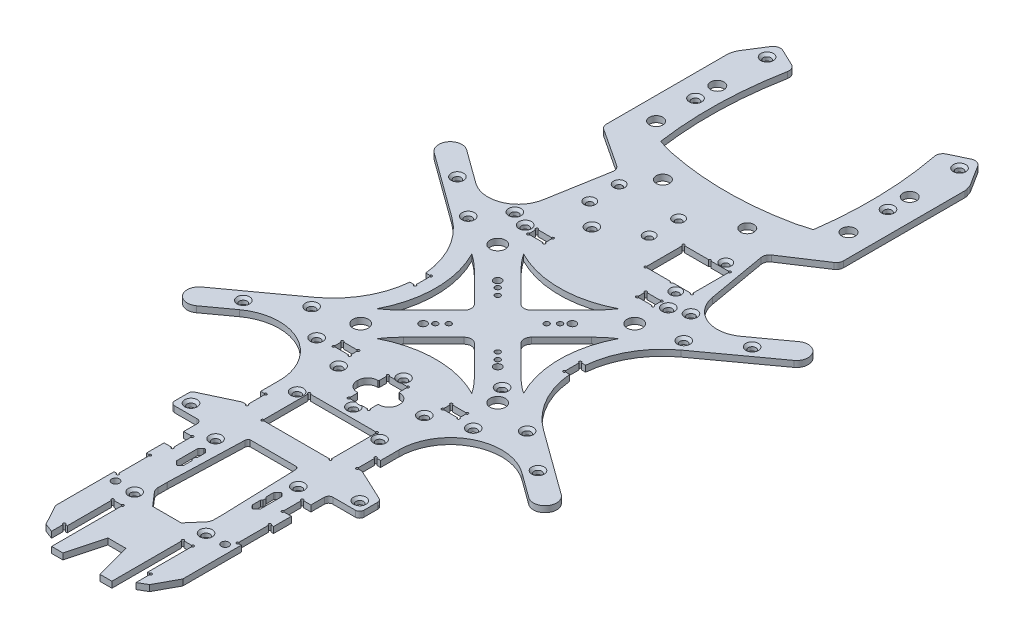
SolidWorks part; units mm, degrees
material "PPS"
ref_plane "前视基准面" through (0, 0, 0) normal (0, 0, 1) x (1, 0, 0)
ref_plane "上视基准面" through (0, 0, 0) normal (0, 1, 0) x (1, 0, 0)
ref_plane "右视基准面" through (0, 0, 0) normal (1, 0, 0) x (0, 0, -1)
sketch "草图1" plane through (0, 0, 0) normal (0, 1, 0) x (1, 0, 0)
  line L0 (-126.4995, 0) -> (116.8967, 0) construction
  line L1 (121.619, 121.619) -> (-121.619, -121.619) construction
  line L2 (0, 104.5414) -> (0, -99.6328) construction
  line L3 (-108.3893, 108.3893) -> (124.9236, -124.9236) construction
  line L4 (0, 0) -> (86.3378, -62.728) construction
  line L5 (21.4, 65.75) -> (28.6, 65.75)
  line L6 (20.9, 50.75) -> (20.9, 65.25)
  line L19 (21.4, 50.25) -> (28.6, 50.25)
  line L20 (30.0249, 79.2189) -> (48.4165, 91.3178)
  line L21 (0, 82.79) -> (0, 88.225) construction
  line L23 (-25.2781, 96.1111) -> (-31.2329, 97.7907)
  line L25 (24.5, -95.1) -> (26, -95.1) construction
  line L35 (73.5338, -47.5541) -> (46.853, -28.1694)
  line L38 (-14.1474, -105.2622) -> (-15.2326, -104.177)
  line L39 (-48.4165, 91.3178) -> (-48.4165, 143.0516)
  line L40 (-30.0249, 79.2189) -> (-48.4165, 91.3178)
  line L42 (26, -95.1) -> (26, -102.35)
  line L64 (20.9, 58) -> (32.4846, 58) construction
  line L65 (25, 65.75) -> (25, 50.25) construction
  line L66 (29.1, 65.25) -> (29.1, 50.75)
  line L69 (-39.335, 68.135) -> (3.7462, 68.135) construction
  line L72 (26, -102.35) -> (22.5, -102.35)
  line L80 (-15.9397, -104.177) -> (-16.9545, -105.1918)
  line L82 (4.1009, -56.25) -> (4.1009, -53.2975)
  line L83 (-3.6009, -56.75) -> (3.6009, -56.75)
  line L84 (3.6009, -40.75) -> (-3.5991, -40.75)
  line L85 (4.1009, -41.25) -> (4.1009, -44.2025)
  line L86 (-4.1009, -56.25) -> (-4.1009, -53.2961)
  line L87 (-4.1009, -44.2011) -> (-4.1009, -41.2481)
  line L88 (-4.5484, -52.9461) -> (-4.4509, -52.9461)
  line L89 (-8.5484, -48.9461) -> (-8.5484, -48.5511)
  line L90 (8.5484, -48.9475) -> (8.5484, -48.5525)
  line L91 (4.4509, -52.9475) -> (4.5484, -52.9475)
  line L92 (4.5484, -44.5525) -> (4.4509, -44.5525)
  line L93 (-4.5484, -44.5511) -> (-4.4509, -44.5511)
  line L97 (19, -62.5) -> (19, -100.5) construction
  line L98 (19, -100.5) -> (-19, -100.5) construction
  line L99 (-19, -62.5) -> (-19, -100.5) construction
  line L100 (22.5, -102.35) -> (22.5, -110.35)
  line L101 (16.4174, -141.0041) -> (16.4174, -159.5041)
  line L102 (16.4174, -141.0041) -> (12.3174, -141.0041)
  line L103 (12.3174, -141.0041) -> (12.3174, -170.0041)
  line L104 (17.705, -159.5041) -> (16.4174, -159.5041)
  line L105 (17.705, -165.5542) -> (17.705, -159.5041)
  line L106 (-3.8169, -155.5041) -> (-7.6919, -170.0041)
  line L107 (-7.6919, -170.0041) -> (-12.3174, -170.0041)
  line L108 (21.2406, -163.4622) -> (17.705, -165.5542)
  line L109 (-17.705, -164.6632) -> (-17.705, -159.5041)
  line L110 (-17.705, -159.5041) -> (-16.4174, -159.5041)
  line L111 (-12.3174, -141.0041) -> (-12.3174, -170.0041)
  line L112 (-16.4174, -141.0041) -> (-12.3174, -141.0041)
  line L113 (-16.4174, -141.0041) -> (-16.4174, -159.5041)
  line L114 (7.4592, -170.0041) -> (12.3174, -170.0041)
  line L115 (-3.8169, -155.5041) -> (3.6009, -155.5041)
  line L116 (3.6009, -155.5041) -> (7.4592, -170.0041)
  line L117 (-21.3412, -163.277) -> (-17.705, -164.6632)
  line L118 (-11.3955, -123.6362) -> (-10.3849, -92.9161)
  line L119 (-10.5767, -129.7197) -> (-5.85, -135.1929)
  line L120 (-5.85, -135.1929) -> (5.85, -135.1929)
  line L121 (-11.3974, -127.5138) -> (-11.3974, -123.7472)
  line L122 (22.5, -110.35) -> (26, -110.35)
  line L123 (26, -130.7962) -> (26, -154.7028)
  line L124 (26, -154.7028) -> (21.2406, -163.4622)
  line L125 (-26, -154.7028) -> (-21.3412, -163.277)
  line L126 (-26, -130.7962) -> (-26, -154.7028)
  line L127 (26, -110.35) -> (26, -117.6)
  line L128 (26, -117.6) -> (24.5, -117.6)
  line L129 (24.5, -117.6) -> (24.5, -130.7962)
  line L130 (24.5, -130.7962) -> (26, -130.7962)
  line L132 (-24.5, -130.7962) -> (-26, -130.7962)
  line L133 (-24.5, -117.6) -> (-24.5, -130.7962)
  line L134 (-26, -117.6) -> (-24.5, -117.6)
  line L135 (-26, -110.35) -> (-26, -117.6)
  line L136 (-22.5, -110.35) -> (-26, -110.35)
  line L137 (-22.5, -102.35) -> (-22.5, -110.35)
  line L138 (-26, -102.35) -> (-22.5, -102.35)
  line L139 (-26, -95.1) -> (-26, -102.35)
  line L140 (-24.5, -95.1) -> (-26, -95.1) construction
  line L142 (-73.5338, 47.5541) -> (-46.853, 28.1694)
  line L143 (-73.5338, -47.5541) -> (-46.853, -28.1694)
  line L149 (48.4165, 91.3178) -> (48.4165, 143.0516)
  line L150 (0, -114.8485) -> (0, -146.3095) construction
  line L151 (-9.5, -91.6929) -> (9.5, -91.6929)
  line L152 (10.5767, -129.7197) -> (5.85, -135.1929)
  line L153 (11.3974, -127.5138) -> (11.3974, -123.7472)
  line L154 (11.3955, -123.6362) -> (10.3849, -92.9161)
  line L155 (-19, -62.5) -> (19, -62.5) construction
  line L166 (-13.866, -63.21) -> (13.866, -63.21)
  line L171 (-13.866, -63.21) -> (-13.866, -82.21)
  line L174 (-13.866, -82.21) -> (13.866, -82.21)
  line L177 (13.866, -63.21) -> (13.866, -82.21)
  line L180 (73.5338, 47.5541) -> (46.853, 28.1694)
  line L181 (44.0442, 32) -> (60.2246, 43.7557) construction
  line L183 (25.2781, 96.1111) -> (31.2329, 97.7907)
  line L184 (47.6512, 145.4189) -> (48.4165, 143.0516)
  line L188 (-47.6512, 145.4189) -> (-40.8875, 156.1591)
  line L190 (47.6512, 145.4189) -> (40.8875, 156.1591)
  line L192 (31.6811, 151.7709) -> (40.8875, 156.1591)
  line L193 (-40.8875, 156.1591) -> (-31.6811, 151.7709)
  line L194 (-47.6512, 145.4189) -> (-48.4165, 143.0516)
  line L195 (67.9498, 55.2397) -> (54.1532, 45.2159)
  line L196 (30.0249, 79.2189) -> (34.5797, 53.1425)
  line L197 (-30.0249, 79.2189) -> (-34.5797, 53.1425)
  line L198 (-67.9498, 55.2397) -> (-54.1532, 45.2159)
  line L199 (57.77, -47.8437) -> (67.9498, -55.2397)
  line L200 (24.5, -64.7956) -> (24.5, -95.1) construction
  line L201 (-24.5, -64.7956) -> (-24.5, -95.1) construction
  line L202 (-57.77, -47.8437) -> (-67.9498, -55.2397)
  line L203 (26, -95.1) -> (38.6804, -95.1)
  line L204 (38.6804, -95.1) -> (38.6804, -86.6)
  line L205 (38.6804, -86.6) -> (24.5, -79.9478)
  line L207 (-38.6804, -86.6) -> (-24.5, -79.9478)
  line L208 (-38.6804, -95.1) -> (-38.6804, -86.6)
  line L209 (-26, -95.1) -> (-38.6804, -95.1)
  line L210 (-24.5, -64.7956) -> (-24.5, -79.9478) construction
  line L211 (-16.9545, -114.3989) -> (-15.8693, -115.4841)
  line L212 (-15.1622, -115.4841) -> (-14.1474, -114.4693)
  line L213 (-17.1009, -105.5454) -> (-17.1009, -114.0454)
  line L214 (-14.0009, -105.6158) -> (-14.0009, -114.1158) construction
  line L221 (-14.0009, -105.6158) -> (-14.0009, -108.6704)
  line L222 (-14.0009, -108.6704) -> (-14.5009, -109.1704)
  line L223 (-14.5009, -109.1704) -> (-14.5009, -110.4204)
  line L224 (-14.5009, -110.4204) -> (-14.0009, -110.9204)
  line L225 (-14.0009, -110.9204) -> (-14.0009, -114.1158)
  line L226 (-17.1009, -109.7954) -> (-13.2317, -109.7954) construction
  line L227 (14.5009, -110.4204) -> (14.0009, -110.9204)
  line L228 (14.5009, -109.1704) -> (14.5009, -110.4204)
  line L229 (14.0009, -108.6704) -> (14.5009, -109.1704)
  line L230 (14.0009, -105.6158) -> (14.0009, -108.6704)
  line L231 (14.1474, -105.2622) -> (15.2326, -104.177)
  line L232 (15.9397, -104.177) -> (16.9545, -105.1918)
  line L233 (17.1009, -105.5454) -> (17.1009, -114.0454)
  line L234 (16.9545, -114.3989) -> (15.8693, -115.4841)
  line L235 (15.1622, -115.4841) -> (14.1474, -114.4693)
  line L236 (14.0009, -110.9204) -> (14.0009, -114.1158)
  line L237 (-24.5, -72.3717) -> (-22.5, -72.3717)
  line L238 (-22.5, -72.3717) -> (-22.5, -79.9478)
  line L239 (-22.5, -79.9478) -> (-24.5, -79.9478)
  line L240 (-24.5, -64.7956) -> (-24.5, -72.3717)
  line L241 (22.5, -79.9478) -> (24.5, -79.9478)
  line L242 (24.5, -64.7956) -> (24.5, -72.3717)
  line L243 (24.5, -72.3717) -> (22.5, -72.3717)
  line L244 (22.5, -72.3717) -> (22.5, -79.9478)
  circle A0 centre (10, 10) radius 1.075
  circle A1 centre (12.75, 12.75) radius 1.075
  circle A2 centre (15.25, 15.25) radius 1.55
  circle A3 centre (-15.25, 15.25) radius 1.55
  circle A4 centre (-12.75, 12.75) radius 1.075
  circle A5 centre (-10, 10) radius 1.075
  circle A6 centre (-10, -10) radius 1.075
  circle A7 centre (-12.75, -12.75) radius 1.075
  circle A8 centre (-15.25, -15.25) radius 1.55
  circle A9 centre (15.25, -15.25) radius 1.55
  circle A10 centre (12.75, -12.75) radius 1.075
  circle A11 centre (10, -10) radius 1.075
  circle A14 centre (28, -28) radius 3.15
  circle A15 centre (-28, -28) radius 3.15
  circle A16 centre (25, 68.2) radius 1.3
  arc A17 (20.9, 65.25) -> (21.4, 65.75) centre (20.9, 65.75) cw
  arc A18 (20.9, 50.75) -> (21.4, 50.25) centre (20.9, 50.25) ccw
  circle A31 centre (25, 47.8) radius 1.3
  circle A34 centre (17.238, 84.7633) radius 2.75
  circle A35 centre (-17.238, 84.7633) radius 2.75
  circle A36 centre (-39.335, 104.0823) radius 2.75
  circle A37 centre (-39.335, 129.0823) radius 2.75
  circle A38 centre (-28, 28) radius 3.15
  circle A39 centre (28, 28) radius 3.15
  circle A43 centre (44.0442, -32) radius 1.55
  circle A44 centre (60.2246, -43.7557) radius 1.55
  circle A47 centre (-60.2246, -43.7557) radius 1.55
  arc A63 (29.1, 65.25) -> (28.6, 65.75) centre (29.1, 65.75) ccw
  arc A64 (29.1, 50.75) -> (28.6, 50.25) centre (29.1, 50.25) cw
  circle A65 centre (-24.5, 74.15) radius 1.3
  circle A68 centre (-24.5, 62.12) radius 1.3
  circle A71 centre (-44.0442, -32) radius 1.55
  circle A72 centre (60.2246, 43.7557) radius 1.55
  circle A73 centre (44.0442, 32) radius 1.55
  circle A74 centre (-44.0442, 32) radius 1.55
  circle A75 centre (-60.2246, 43.7557) radius 1.55
  arc A77 (67.9498, -55.2397) -> (73.5338, -47.5541) centre (70.7418, -51.3969) ccw
  arc A82 (-14.0009, -105.6158) -> (-14.1474, -105.2622) centre (-14.5009, -105.6158) ccw
  arc A83 (-15.2326, -104.177) -> (-15.9397, -104.177) centre (-15.5861, -104.5306) ccw
  arc A84 (-17.1009, -105.5454) -> (-16.9545, -105.1918) centre (-16.6009, -105.5454) cw
  arc A85 (-4.1009, -56.25) -> (-3.6009, -56.75) centre (-4.1009, -56.75) ccw
  arc A86 (4.1009, -56.25) -> (3.6009, -56.75) centre (4.1009, -56.75) cw
  arc A87 (4.1009, -41.25) -> (3.6009, -40.75) centre (4.1009, -40.75) ccw
  arc A88 (-4.1009, -41.2481) -> (-3.5991, -40.75) centre (-4.0991, -40.7481) cw
  arc A89 (8.5484, -48.5525) -> (4.5484, -44.5525) centre (4.5484, -48.5525) ccw
  arc A90 (-4.5484, -44.5511) -> (-8.5484, -48.5511) centre (-4.5484, -48.5511) ccw
  arc A91 (-4.5484, -52.9461) -> (-8.5484, -48.9461) centre (-4.5484, -48.9461) cw
  arc A92 (8.5484, -48.9475) -> (4.5484, -52.9475) centre (4.5484, -48.9475) cw
  arc A93 (4.1009, -44.2025) -> (4.4509, -44.5525) centre (4.4509, -44.2025) ccw
  arc A94 (4.1009, -53.2975) -> (4.4509, -52.9475) centre (4.4509, -53.2975) cw
  arc A95 (-4.1009, -44.2011) -> (-4.4509, -44.5511) centre (-4.4509, -44.2011) cw
  arc A96 (-4.1009, -53.2961) -> (-4.4509, -52.9461) centre (-4.4509, -53.2961) ccw
  circle A103 centre (-22.3899, -133.8062) radius 1.55
  circle A104 centre (22.3899, -133.8062) radius 1.55
  circle A105 centre (-16.9, -98.4) radius 1.55
  circle A106 centre (16.9, -98.4) radius 1.55
  arc A107 (-9.5, -91.6929) -> (-10.3849, -92.9161) centre (-9.0356, -92.9605) ccw
  arc A108 (-11.3974, -123.7472) -> (-11.3955, -123.6362) centre (-8.0224, -123.7472) cw
  arc A109 (-10.5767, -129.7197) -> (-11.3974, -127.5138) centre (-8.0224, -127.5138) cw
  circle A110 centre (-14.6009, -133.8062) radius 1.55
  circle A111 centre (14.6009, -133.8062) radius 1.55
  arc A112 (10.5767, -129.7197) -> (11.3974, -127.5138) centre (8.0224, -127.5138) ccw
  arc A113 (11.3974, -123.7472) -> (11.3955, -123.6362) centre (8.0224, -123.7472) ccw
  arc A114 (9.5, -91.6929) -> (10.3849, -92.9161) centre (9.0356, -92.9605) cw
  circle A143 centre (-16.866, -65.108) radius 1.55
  circle A144 centre (16.866, -65.108) radius 1.55
  circle A145 centre (0, -38.5) radius 1.55
  circle A146 centre (0, -59) radius 1.55
  arc A147 (67.9498, 55.2397) -> (73.5338, 47.5541) centre (70.7418, 51.3969) cw
  arc A148 (46.853, 28.1694) -> (46.853, -28.1694) centre (67.3193, 0) ccw
  circle A149 centre (44.0442, -32) radius 6 construction
  arc A151 (-67.9498, 55.2397) -> (-73.5338, 47.5541) centre (-70.7418, 51.3969) ccw
  arc A153 (-46.853, 28.1694) -> (-46.853, -28.1694) centre (-67.3193, 0) cw
  arc A154 (-67.9498, -55.2397) -> (-73.5338, -47.5541) centre (-70.7418, -51.3969) cw
  circle A158 centre (39.335, 129.0823) radius 2.75
  circle A159 centre (39.335, 104.0823) radius 2.75
  arc A160 (-25.2781, 96.1111) -> (25.2781, 96.1111) centre (0, 215.2587) ccw
  circle A161 centre (-36, 43) radius 1.55
  circle A164 centre (36, 43) radius 1.55
  circle A165 centre (-32, -42) radius 1.55
  circle A166 centre (32, -42) radius 1.55
  circle A171 centre (-39.335, 149.4323) radius 1.55
  arc A176 (30.0249, 148.5011) -> (31.6811, 151.7709) centre (32.9719, 149.0628) cw
  arc A178 (30.0249, 148.5011) -> (31.2329, 97.7907) centre (-122.0773, 119.5082) cw
  arc A180 (-30.0249, 148.5011) -> (-31.2329, 97.7907) centre (122.0773, 119.5082) ccw
  arc A181 (-31.6811, 151.7709) -> (-30.0249, 148.5011) centre (-32.9719, 149.0628) cw
  arc A182 (54.1532, 45.2159) -> (34.5797, 53.1425) centre (46.8385, 55.2837) cw
  arc A183 (-54.1532, 45.2159) -> (-34.5797, 53.1425) centre (-46.8385, 55.2837) ccw
  circle A185 centre (39.335, 149.4323) radius 1.55
  arc A186 (57.77, -47.8437) -> (24.5, -64.7956) centre (45.4537, -64.7956) ccw
  arc A187 (-57.77, -47.8437) -> (-24.5, -64.7956) centre (-45.4537, -64.7956) cw
  circle A188 centre (34.5, -90.85) radius 1.55
  circle A189 centre (-34.5, -90.85) radius 1.55
  circle A190 centre (39.335, 120.1823) radius 1.55
  circle A191 centre (-39.335, 120.1823) radius 1.55
  arc A192 (-17.1009, -114.0454) -> (-16.9545, -114.3989) centre (-16.6009, -114.0454) ccw
  arc A193 (-15.8693, -115.4841) -> (-15.1622, -115.4841) centre (-15.5157, -115.1306) ccw
  arc A194 (-14.0009, -114.1158) -> (-14.1474, -114.4693) centre (-14.5009, -114.1158) cw
  arc A195 (14.0009, -105.6158) -> (14.1474, -105.2622) centre (14.5009, -105.6158) cw
  arc A196 (15.2326, -104.177) -> (15.9397, -104.177) centre (15.5861, -104.5306) cw
  arc A197 (17.1009, -105.5454) -> (16.9545, -105.1918) centre (16.6009, -105.5454) ccw
  arc A198 (17.1009, -114.0454) -> (16.9545, -114.3989) centre (16.6009, -114.0454) cw
  arc A199 (15.8693, -115.4841) -> (15.1622, -115.4841) centre (15.5157, -115.1306) cw
  arc A200 (14.0009, -114.1158) -> (14.1474, -114.4693) centre (14.5009, -114.1158) ccw
  circle A201 centre (-0.2, 62.12) radius 1.3
  circle A202 centre (-0.2, 74.15) radius 1.3
  point P104 (-32.5, 0)
  point P105 (32.5, 0)
  point P214 (38.6804, -90.85)
  point P354 (0, -135.1929)
  point P361 (7.3036, -118.1341)
  point P364 (0, -91.6929)
  dimension "D2" = 2.15
  dimension "D5" = 3.1
  dimension "D7" = 3.1
  dimension "D8" = 36
  dimension "D10" = 0.5
  dimension "D11" = 3.1
  dimension "D20" = 2.6
  dimension "D22" = 3.1
  dimension "D32" = 7.25
  dimension "D12" = 24.3
  dimension "D15" = 19
  dimension "D13" = 3
  dimension "D9" = 3.1
  dimension "D25" = 4.75
  dimension "D26" = 13
  dimension "D31" = 12
  dimension "D41" = 96.833
  dimension "D49" = 32
  dimension "D54" = 45.35
  dimension "D59" = 8.5
  dimension "D61" = 6.3
  dimension "D70" = 2.6
  dimension "D3" = 10
  dimension "D4" = 2.75
  dimension "D6" = 2.5
  dimension "D14" = 58
  dimension "D16" = 2.608
  dimension "D17" = 15.5
  dimension "D18" = 2.45
  dimension "D19" = 8.2
  dimension "D21" = 12.03
  dimension "D23" = 2.25
  dimension "D24" = 2.25
  dimension "D27" = 20
  dimension "D28" = 25
  dimension "D29" = 25
  dimension "D30" = 32
  dimension "D33" = 1.5
  dimension "D34" = 2.1
  dimension "D35" = 10.5
  dimension "D36" = 14.5
  dimension "D37" = 4
  dimension "D38" = 4.1
  dimension "D39" = 8
  dimension "D40" = 65
  dimension "D42" = 9.5
  dimension "D43" = 43
  dimension "D44" = 43.5
  dimension "D45" = 40.75
  dimension "D46" = 7.2
  dimension "D47" = 16
  dimension "D48" = 62.5
  dimension "D50" = 38
  dimension "D51" = 7.2
  dimension "D52" = 36
  dimension "D53" = 42
  dimension "D55" = 90.85
  dimension "D56" = 5.5
  dimension "D57" = 38
  dimension "D58" = 34.5
  dimension "D60" = 56
  dimension "D62" = 5.85
  dimension "D63" = 29.25
  dimension "D64" = 8.5
  dimension "D65" = 1.25
  dimension "D66" = 0.5
  dimension "D67" = 2
  dimension "D68" = 24.5
  dimension "D69" = 82.21
extrude "凸台-拉伸1" add sketch "草图1" along normal blind 2.5
sketch "草图6" plane through (0, 2.5, 0) normal (0, 1, 0) x (1, 0, 0)
  line L1 (-23.978, 14.4296) -> (-9.5485, 0)
  line L2 (-126.4995, 0) -> (116.8967, 0) construction
  line L3 (-58.8867, 0) -> (57.6096, 0) construction
  line L4 (-23.978, -14.4296) -> (-9.5485, 0)
  line L5 (0, 29.8455) -> (0, -115.5328) construction
  line L6 (0, 104.5414) -> (0, -99.6328) construction
  line L14 (14.4296, 23.978) -> (0, 9.5485)
  line L15 (-14.4296, 23.978) -> (0, 9.5485)
  line L27 (23.978, -14.4296) -> (9.5485, 0)
  line L28 (23.978, 14.4296) -> (9.5485, 0)
  line L29 (-14.4296, -23.978) -> (0, -9.5485)
  line L30 (14.4296, -23.978) -> (0, -9.5485)
  arc A3 (-23.978, 14.4296) -> (-29.9602, 19.3706) centre (-52.8883, -14.4807) ccw
  arc A5 (-23.978, -14.4296) -> (-29.9602, -19.3706) centre (-52.8883, 14.4807) cw
  arc A6 (-29.9602, -19.3706) -> (-29.9602, 19.3706) centre (-67.3193, 0) ccw
  arc A18 (-14.4296, 23.978) -> (-19.3706, 29.9602) centre (14.4807, 52.8883) cw
  arc A19 (-19.3706, 29.9602) -> (19.3706, 29.9602) centre (0, 67.3193) ccw
  arc A20 (14.4296, 23.978) -> (19.3706, 29.9602) centre (-14.4807, 52.8883) ccw
  arc A30 (23.978, 14.4296) -> (29.9602, 19.3706) centre (52.8883, -14.4807) cw
  arc A31 (29.9602, 19.3706) -> (29.9602, -19.3706) centre (67.3193, 0) ccw
  arc A32 (23.978, -14.4296) -> (29.9602, -19.3706) centre (52.8883, 14.4807) ccw
  arc A33 (14.4296, -23.978) -> (19.3706, -29.9602) centre (-14.4807, -52.8883) cw
  arc A34 (19.3706, -29.9602) -> (-19.3706, -29.9602) centre (0, -67.3193) ccw
  arc A35 (-14.4296, -23.978) -> (-19.3706, -29.9602) centre (14.4807, -52.8883) ccw
  dimension "D1" = 45
  dimension "D2" = 4
extrude "减重" cut sketch "草图6" against normal up to next
fillet "圆角1" radius 3 14 edges at (-25.2781, 1.25, -96.1111) (25.2781, 1.25, -96.1111) (48.4165, 1.25, -91.3178) (-48.4165, 1.25, -91.3178) (-9.5485, 1.25, 0) (9.5485, 1.25, 0) (0, 1.25, -9.5485) (0, 1.25, 9.5485) (48.4165, 1.25, -143.0516) (40.8875, 1.25, -156.1591) (-48.4165, 1.25, -143.0516) (-40.8875, 1.25, -156.1591) (-30.0249, 1.25, -79.2189) (30.0249, 1.25, -79.2189)
sketch "草图7" plane through (0, 2.5, 0) normal (0, 1, 0) x (1, 0, 0)
  line L0 (-81.2345, 0) -> (102.1666, 0) construction
  line L1 (0, 63.5408) -> (0, -83.9036) construction
  line L2 (34, -3.25) -> (30.5, -3.25)
  line L3 (-34, 3.25) -> (-30.5, 3.25)
  line L4 (-34, 3.25) -> (-34, -3.25)
  line L5 (-34, -3.25) -> (-30.5, -3.25)
  line L6 (-30.5, 3.25) -> (-30.5, -3.25)
  line L7 (30.5, 3.25) -> (30.5, -3.25)
  line L8 (34, 3.25) -> (30.5, 3.25)
  line L9 (34, 3.25) -> (34, -3.25)
  line L10 (19, -38) -> (25.5, -38)
  line L11 (-25.5, 41.5) -> (-19, 41.5)
  line L12 (-25.5, 41.5) -> (-25.5, 38)
  line L13 (-25.5, 38) -> (-19, 38)
  line L14 (-19, 41.5) -> (-19, 38)
  line L15 (19, -38) -> (19, -41.5)
  line L16 (19, -41.5) -> (25.5, -41.5)
  line L17 (25.5, -38) -> (25.5, -41.5)
  line L18 (-19, -38) -> (-19, -41.5)
  line L19 (-19, -41.5) -> (-25.5, -41.5)
  line L20 (-25.5, -38) -> (-25.5, -41.5)
  line L21 (-19, -38) -> (-25.5, -38)
  line L22 (25.5, 38) -> (19, 38)
  line L23 (19, 41.5) -> (19, 38)
  line L24 (25.5, 41.5) -> (19, 41.5)
  line L25 (25.5, 41.5) -> (25.5, 38)
  point P26 (19, -39.75)
  dimension "D1" = 3.5
  dimension "D2" = 6.5
  dimension "D3" = 30.5
  dimension "D4" = 38
  dimension "D5" = 19
  dimension "D6" = 38
extrude "保护壳固定点" cut sketch "草图7" against normal up to next
sketch "草图8" plane through (0, 0, 0) normal (0, 1, 0) x (1, 0, 0)
  line L5 (0, 0) -> (0, 133.3353) construction
  line L6 (0, 0) -> (133.1914, 0) construction
  line L7 (10.15, 65.7804) -> (20.9, 65.7804)
  line L8 (20.9, 65.25) -> (20.9, 50.75) construction
  line L9 (20.9, 65.7804) -> (20.9, 50.2804)
  line L10 (20.9, 50.2804) -> (10.15, 50.2804)
  line L11 (10.15, 50.2804) -> (10.15, 65.7804)
  line L12 (19.65, 65.7804) -> (19.65, 50.2804) construction
  circle A0 centre (23.5, -21.7128) radius 1.55
  circle A1 centre (0, -38.5) radius 1.55 construction
  circle A2 centre (-29.25, 40.5) radius 1.55
  circle A4 centre (-17.5, -47.5) radius 1.55
  circle A6 centre (29.25, 40.5) radius 1.55
  circle A7 centre (17.5, -47.5) radius 1.55
  circle A8 centre (29.25, 40.5) radius 1.55
  dimension "D3" = 3.1
  dimension "D9" = 40.5
  dimension "D12" = 3.1
  dimension "D1" = 16.7872
  dimension "D2" = 23.5
  dimension "D4" = 1.25
  dimension "D6" = 9.5
  dimension "D7" = 15.5
  dimension "D8" = 29.25
  dimension "D10" = 47.5
  dimension "D11" = 17.5
extrude "计算机板接口和分电PCB接口" cut sketch "草图8" along normal through all contours L11 L10 L9 L7 | A2 | A4 | A7 | A6 | A0 | A0 region at (15.525, 0, -58.0304) region at (23.5, 0, 21.7128) region at (-29.25, 0, -40.5) region at (-17.5, 0, 47.5) region at (29.25, 0, -40.5) region at (17.5, 0, 47.5)
fillet "圆角2" radius 1.75 8 edges at (-26, 1.25, 95.1) (-38.6804, 1.25, 95.1) (-38.6804, 1.25, 86.6) (38.6804, 1.25, 86.6) (38.6804, 1.25, 95.1) (26, 1.25, 95.1) (24.5, 1.25, 79.9478) (-24.5, 1.25, 79.9478)
chamfer "沉头螺丝位" distance 1 angle 45 37 edges at (14.6009, 2.5, 135.3562) (-14.6009, 2.5, 132.2562) (0, 2.5, 40.05) (0, 2.5, 60.55) (25, 2.5, -49.1) (25, 2.5, -69.5) (-24.5, 2.5, -63.42) (-24.5, 2.5, -72.85) (60.2246, 2.5, -45.3057) (44.0442, 2.5, -33.55) (36, 2.5, -44.55) (-60.2246, 2.5, -42.2057) (-36, 2.5, -41.45) (-44.0442, 2.5, -30.45) (-32, 2.5, 43.55) (-44.0442, 2.5, 30.45) (-60.2246, 2.5, 42.2057) (60.2246, 2.5, 45.3057) (44.0442, 2.5, 33.55) (32, 2.5, 40.45) (16.866, 2.5, 63.558) (-16.866, 2.5, 66.658) (-16.9, 2.5, 99.95) (16.9, 2.5, 96.85) (34.5, 2.5, 92.4) (-34.5, 2.5, 89.3) (39.335, 2.5, -147.8823) (-39.335, 2.5, -147.8823) (23.5, 2.5, 23.2628) (29.25, 2.5, -38.95) (-29.25, 2.5, -38.95) (-17.5, 2.5, 49.05) (17.5, 2.5, 49.05) (39.335, 2.5, -118.6323) (-39.335, 2.5, -121.7323) (-0.2, 2.5, -75.45) (-0.2, 2.5, -60.82)
sketch "这个是因为刀切不了直角" plane through (0, 2.5, 0) normal (0, 1, 0) x (1, 0, 0)
  line L1 (-17.705, -164.6632) -> (-17.705, -159.5041) construction
  line L2 (0, 0) -> (0, -194.9857) construction
  circle A0 centre (10.15, 65.7804) radius 0.5
  circle A1 centre (10.15, 50.2804) radius 0.5
  circle A2 centre (-25.5, 41.5) radius 0.5
  circle A3 centre (-19, 41.5) radius 0.5
  circle A4 centre (-25.5, 38) radius 0.5
  circle A5 centre (-19, 38) radius 0.5
  circle A14 centre (-25.5, -38) radius 0.5
  circle A15 centre (-19, -38) radius 0.5
  circle A16 centre (-25.5, -41.5) radius 0.5
  circle A17 centre (-19, -41.5) radius 0.5
  circle A28 centre (-13.866, -82.21) radius 0.5
  circle A30 centre (-13.866, -63.21) radius 0.5
  circle A31 centre (-22.5, -72.3717) radius 0.5
  circle A33 centre (-22.5, -79.9478) radius 0.5
  circle A35 centre (-22.5, -102.35) radius 0.5
  circle A37 centre (-22.5, -110.35) radius 0.5
  circle A39 centre (-24.5, -117.6) radius 0.5
  circle A40 centre (-16.4174, -141.0041) radius 0.5
  circle A41 centre (-24.5, -130.7962) radius 0.5
  circle A42 centre (-12.3174, -141.0041) radius 0.5
  circle A43 centre (-17.705, -159.5041) radius 0.5
  circle A47 centre (17.705, -159.5041) radius 0.5
  circle A48 centre (12.3174, -141.0041) radius 0.5
  circle A49 centre (24.5, -130.7962) radius 0.5
  circle A50 centre (16.4174, -141.0041) radius 0.5
  circle A51 centre (24.5, -117.6) radius 0.5
  circle A52 centre (22.5, -110.35) radius 0.5
  circle A53 centre (22.5, -102.35) radius 0.5
  circle A54 centre (22.5, -79.9478) radius 0.5
  circle A55 centre (22.5, -72.3717) radius 0.5
  circle A57 centre (13.866, -82.21) radius 0.5
  circle A58 centre (19, -41.5) radius 0.5
  circle A59 centre (25.5, -41.5) radius 0.5
  circle A60 centre (19, -38) radius 0.5
  circle A61 centre (25.5, -38) radius 0.5
  circle A62 centre (19, 38) radius 0.5
  circle A63 centre (25.5, 38) radius 0.5
  circle A64 centre (19, 41.5) radius 0.5
  circle A65 centre (25.5, 41.5) radius 0.5
  circle A66 centre (13.866, -63.21) radius 0.5
  circle A67 centre (-30.5, 3.25) radius 0.5
  circle A69 centre (-30.5, -3.25) radius 0.5
  circle A70 centre (30.5, -3.25) radius 0.5
  circle A71 centre (30.5, 3.25) radius 0.5
  dimension "D1" = 1
extrude "直角约束" cut sketch "这个是因为刀切不了直角" against normal through all
sketch "草图9" plane through (0, 2.5, 0) normal (0, 1, 0) x (1, 0, 0)
  line L0 (26.7, 40.5) -> (-26.7, 40.5) construction
  circle A0 centre (29.25, 40.5) radius 2.55 construction
  circle A1 centre (-29.25, 40.5) radius 2.55 construction
  circle A10 centre (-15, 53.5) radius 1.55
  arc A11 (10.65, 65.7804) -> (10.15, 65.2804) centre (10.15, 65.7804) ccw construction
  dimension "D1" = 3.1
  dimension "D4" = 25.15
  dimension "D5" = 12.2804
  dimension "D2" = 15
  dimension "D3" = 53.5
extrude "计算机板安装孔-旧的太难用了" cut sketch "草图9" against normal blind 10
chamfer "倒角3" distance 1 angle 45 1 edges at (-15, 2.5, -51.95)
